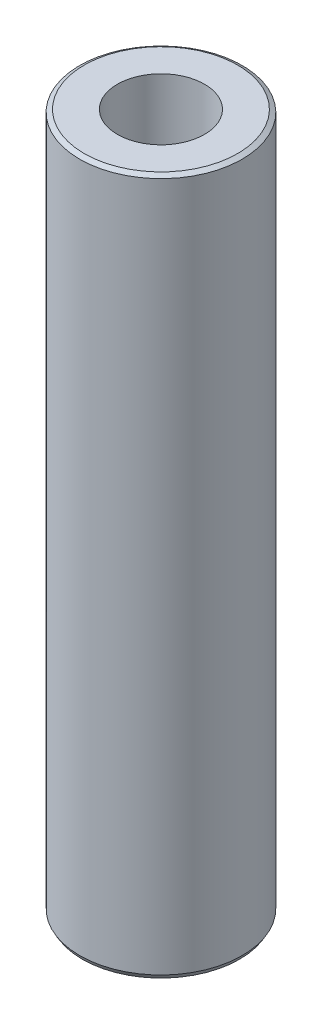
SolidWorks part; units mm, degrees
ref_plane "Front Plane" through (0, 0, 0) normal (0, 0, 1) x (1, 0, 0)
ref_plane "Top Plane" through (0, 0, 0) normal (0, 1, 0) x (1, 0, 0)
ref_plane "Right Plane" through (0, 0, 0) normal (1, 0, 0) x (0, 0, -1)
sketch "Sketch1" plane through (0, 0, 0) normal (0, 1, 0) x (1, 0, 0)
  circle A0 centre (0, 0) radius 42.5
  dimension "SHAFT_OD" = 85
extrude "Boss-Extrude1" add sketch "Sketch1" along normal blind 364.5407
sketch "Sketch2" plane through (0, 0, 0) normal (0, 1, 0) x (1, 0, 0)
  circle A0 centre (0, 0) radius 22.7816
  dimension "BORE_D" = 45.5632
extrude "Cut-Extrude1" cut sketch "Sketch2" along normal through all
chamfer "Chamfer1" distance 1.3669 angle 60 2 edges at (0, 364.5407, 42.5) (0, 0, 42.5) first distance on face at (0, 364.5407, 42.5) first distance on face at (0, 0, 22.7816)
